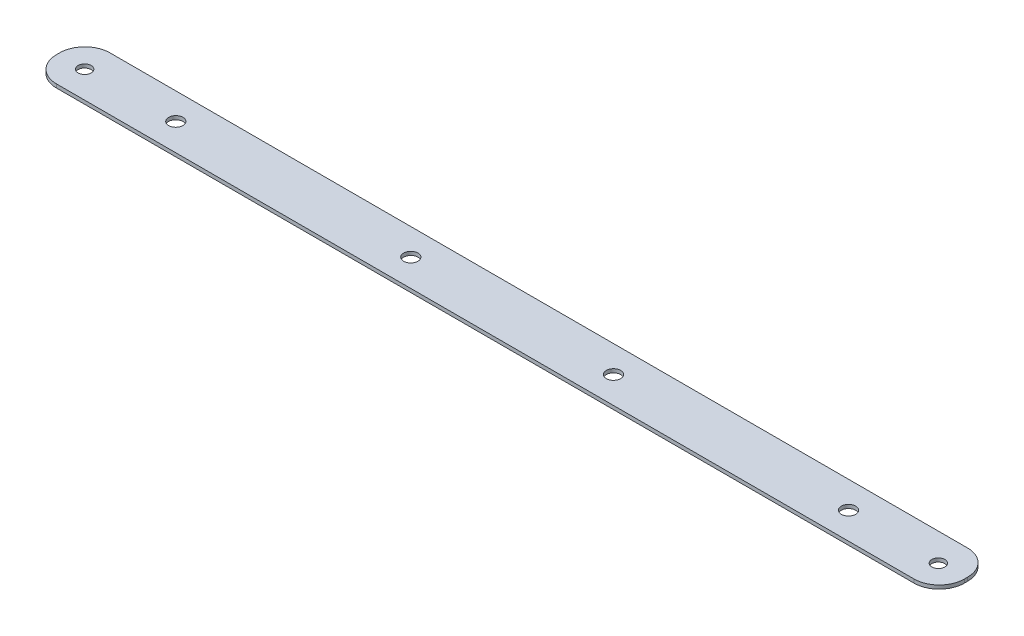
SolidWorks part; units mm, degrees
ref_plane "Front Plane" through (0, 0, 0) normal (0, 0, 1) x (1, 0, 0)
ref_plane "Top Plane" through (0, 0, 0) normal (0, 1, 0) x (1, 0, 0)
ref_plane "Right Plane" through (0, 0, 0) normal (1, 0, 0) x (0, 0, -1)
sketch "Sketch1" plane through (0, 0, 0) normal (0, 1, 0) x (1, 0, 0)
  line L1 (107.95, -6.375) -> (-107.95, -6.375)
  line L2 (107.95, -6.375) -> (107.95, 6.375)
  line L3 (107.95, 6.375) -> (-107.95, 6.375)
  line L4 (-107.95, -6.375) -> (-107.95, 6.375)
  line L5 (107.95, -6.375) -> (-107.95, 6.375) construction
  line L6 (107.95, 6.375) -> (-107.95, -6.375) construction
  circle A0 centre (-101.6, 0) radius 1.55
  point P0 (0, 0)
  dimension "D1" = 215.9
  dimension "D2" = 12.75
base flange "Base-Flange1" sketch "Sketch1" thickness 0.86 reverse thickness direction no parameters "D1"=0.7366
fillet "Fillet1" radius 6 4 edges at (107.95, -0.43, 6.375) (107.95, -0.43, -6.375) (-107.95, -0.43, -6.375) (-107.95, -0.43, 6.375)
ref_plane "Plane1" through (0, -0.86, 6.375) normal (-1, 0, 0) x (0, 0, 1)
hole_wizard "M3 Clearance Hole1" positions "Sketch11" profile "Sketch10" hole size "M3" standard "ANSI Metric"
sketch "Sketch11" plane through (0, 0, 0) normal (0, 1, 0) x (1, 0, 0)
  point P0 (-80.0116, 0.0752)
  point P2 (-24.1316, 0.0752)
  point P6 (80.01, 0)
  point P8 (24.13, 0)
  dimension "D1" = 27.94
  dimension "D2" = 55.88
  dimension "D3" = 55.88
  dimension "D4" = 187.96
sketch "Sketch10" plane through (-80.0116, 0, -0.0752) normal (1, 0, 0) x (0, 0, 1)
  line L0 (0, 0) -> (0, 2.3115)
  line L1 (0, 2.3115) -> (1.7, 1.29)
  line L2 (1.7, 1.29) -> (1.7, 0)
  line L5 (1.7, 0) -> (0, 0)
  line L10 (0, 2.3115) -> (-1.7, 1.29) construction
  line L11 (0, -6.35) -> (0, 107.95) construction
  dimension "Hole Dia." = 3.4
  dimension "Hole Depth" = 1.29
  dimension "Drill Angle" = 118
sketch "Sketch14" plane through (0, 0, 0) normal (0, 1, 0) x (1, 0, 0)
  circle A0 centre (101.6014, -0.2424) radius 1.55
  dimension "D1" = 6.35
extrude "Cut-Extrude1" cut sketch "Sketch14" against normal blind 82 contours A0 normal cut yes
sketch "Bend-Lines1" [suppressed] plane through (0, 0, 0) normal (0, 1, 0) x (1, 0, 0)
sketch "Bounding-Box1" [suppressed] plane through (0, 0, 0) normal (0, 1, 0) x (1, 0, 0)
sheet metal parameters "Sheet-Metal(1)" thickness 0.86 parameters "D1"=0.7366
flat pattern "Flat-Pattern(1)" [suppressed]
sketch "Bend-Lines2" plane through (0, 0, 0) normal (0, 1, 0) x (1, 0, 0)
sketch "Bounding-Box2" [suppressed] plane through (0, 0, 0) normal (0, 1, 0) x (1, 0, 0)
sheet metal parameters "Sheet-Metal(2)" thickness 0.86 parameters "D1"=0.7366
flat pattern "Flat-Pattern(1)"
sketch "Bend-Lines2" plane through (0, 0, 0) normal (0, 1, 0) x (1, 0, 0)
sketch "Bounding-Box2" [suppressed] plane through (0, 0, 0) normal (0, 1, 0) x (1, 0, 0)
sheet metal parameters "Sheet-Metal(4)" thickness 0.86 parameters "D1"=0.7366
flat pattern "Flat-Pattern(1)"
sketch "Bend-Lines2" plane through (0, 0, 0) normal (0, 1, 0) x (1, 0, 0)
sketch "Bounding-Box2" [suppressed] plane through (0, 0, 0) normal (0, 1, 0) x (1, 0, 0)
